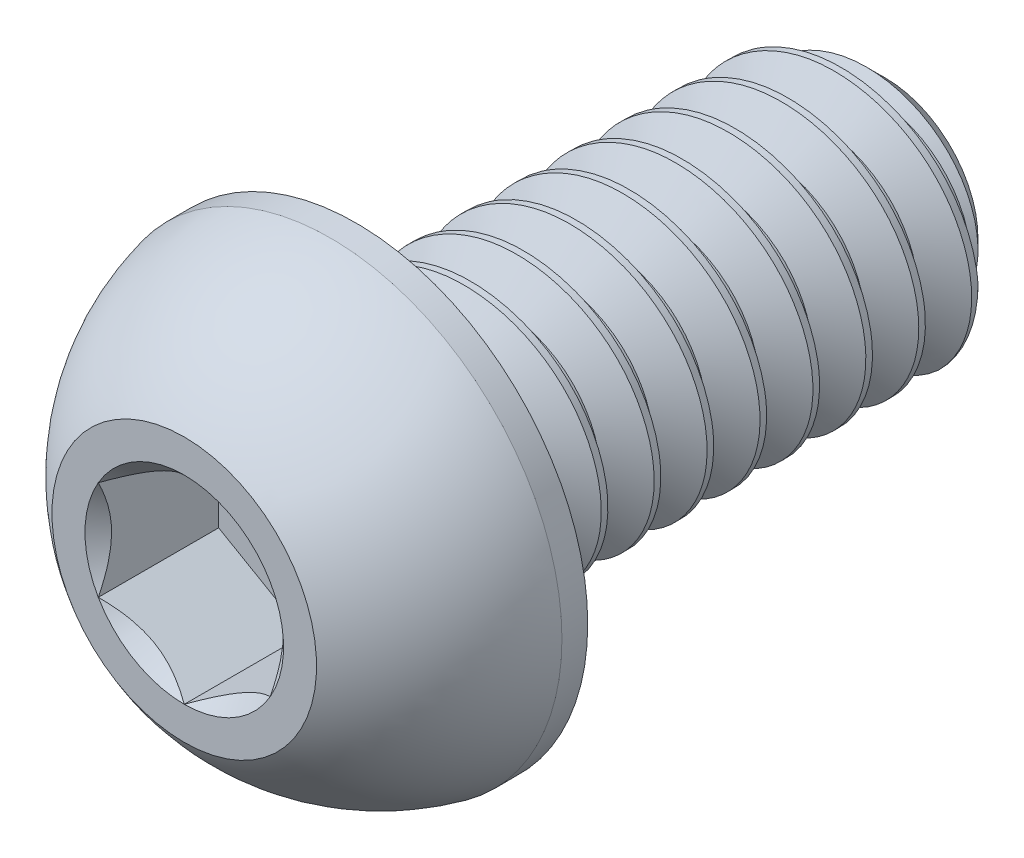
SolidWorks part; units mm, degrees
ref_plane "Front" through (0, 0, 0) normal (0, 0, 1) x (1, 0, 0)
ref_plane "Top" through (0, 0, 0) normal (0, 1, 0) x (1, 0, 0)
ref_plane "Right" through (0, 0, 0) normal (1, 0, 0) x (0, 0, -1)
sketch "Sketch1" plane through (0, 0, 0) normal (1, 0, 0) x (0, 0, -1)
  line L2 (1.3, 1) -> (5.3, 1)
  line L3 (5.3, 1) -> (5.3, 0)
  line L4 (5.3, 0) -> (1.3, 0)
  line L6 (1.105, 1.75) -> (1.3, 1.75) construction
  line L7 (5.3, 1) -> (5.3, -1) construction
  line L8 (0, 0) -> (1.3, 0) construction
  line L9 (1.3, 1.75) -> (1.3, -1.75) construction
  line L11 (1.3, 1) -> (1.3, 0)
  line L13 (0, 0.65) -> (0, -0.65) construction
  line L14 (0, 0.65) -> (0, 1) construction
  arc A3 (0, 1) -> (1.105, 1.75) centre (1.4858, 0) cw construction
  dimension "D1" = 0.195
  dimension "Head Ht" = 1.3
  dimension "Head Dia" = 3.5
  dimension "Dia" = 2
  dimension "Lg" = 4
  dimension "Hex" = 1.3
revolve "Revolve1" add sketch "Sketch1" angle 360 mid plane about L4
sketch "Sketch3" plane through (0, 0, -5.3) normal (0, 0, -1) x (-1, 0, 0)
  circle A0 centre (0, 0) radius 1
curve "Helix/Spiral1" pitch 0.4 height 4.4 radius 1 centre (0, 0, -5.3) axis (0, 0, 1) start towards (0, 1, 0)
sketch "Sketch2" plane through (0, 0, 0) normal (1, 0, 0) x (0, 0, -1)
  line L0 (5.3, 1) -> (5.65, 1)
  line L1 (5.65, 1) -> (5.5, 0.7402)
  line L2 (5.5, 0.7402) -> (5.45, 0.7402)
  line L3 (5.45, 0.7402) -> (5.3, 1)
  line L4 (5.375, 0.8701) -> (5.575, 0.8701) construction
  dimension "D1" = 60
  dimension "D2" = 0.05
  dimension "D3" = 0.2
chamfer "Chamfer1" distance 0.3 angle 45 1 edges at (0, 1, -5.3)
sweep "Cut-Sweep1" cut profiles "Sketch2" path "Helix/Spiral1" align with end faces yes
sketch "Sketch7" plane through (0, 0, 0) normal (1, 0, 0) x (0, 0, -1)
  line L6 (1.105, 1.75) -> (1.3, 1.75) construction
  line L8 (0, 0) -> (1.3, 0) construction
  line L11 (1.3, 1.75) -> (1.3, -1.75) construction
  line L12 (1.105, 1.75) -> (1.3, 1.75)
  line L13 (0, 0) -> (1.3, 0)
  line L14 (0, 0.65) -> (0, -0.65) construction
  line L15 (1.3, 1.75) -> (1.3, 0)
  line L16 (0, 1) -> (0, 0)
  arc A2 (1.105, 1.75) -> (0, 1) centre (1.4858, 0) ccw construction
  arc A3 (1.105, 1.75) -> (0, 1) centre (1.4858, 0) ccw
revolve "Revolve2" add sketch "Sketch7" angle 360 mid plane about L13
sketch "Sketch5" plane through (0, 0, 0) normal (0, 0, 1) x (1, 0, 0)
  line L1 (0.65, -0.3753) -> (0.65, 0.3753)
  line L2 (0.65, 0.3753) -> (0, 0.7506)
  line L3 (0, 0.7506) -> (-0.65, 0.3753)
  line L4 (-0.65, 0.3753) -> (-0.65, -0.3753)
  line L5 (-0.65, -0.3753) -> (0, -0.7506)
  line L6 (0, -0.7506) -> (0.65, -0.3753)
  circle A0 centre (0, 0) radius 0.65 construction
extrude "Cut-Extrude2" cut sketch "Sketch5" against normal blind 0.91
sketch "Sketch6" plane through (0, 0, 0) normal (0, 0, 1) x (1, 0, 0)
  circle A0 centre (0, 0) radius 0.7506
extrude "Cut-Extrude3" cut sketch "Sketch6" against normal blind 0.91 draft 45
sketch "Sketch9" [suppressed] plane through (0, 0, -4.2164) normal (0, 0, 1) x (1, 0, 0)
  circle A2 centre (0, 0) radius 3.9687
extrude "Boss-Extrude2" [suppressed] add sketch "Sketch9" against normal offset from surface (9.525 mm away) 28.575 up to face at (0, 0.7, -5.3)
sketch "Sketch10" plane through (0, 0, 0) normal (1, 0, 0) x (0, 0, -1)
  line L0 (5.3, 1) -> (5.3, -1) construction
  point P0 (4.7, -1)
  dimension "D1" = 0.6
equation "\"D3@Helix/Spiral1\" = \"Lg@Sketch1\" + \"D4@Helix/Spiral1\""
equation "\"D2@Sketch2\" = \"D4@Helix/Spiral1\" * .125"
equation "\"D3@Sketch2\" = \"D4@Helix/Spiral1\" * .5"
equation "\"D1@Chamfer1\" = \"D4@Helix/Spiral1\" * .75"
equation "\"D1@Cut-Extrude2\" = \"Head Ht@Sketch1\" * .7"
equation "\"D1@Sketch1\" = \"Head Ht@Sketch1\" * .15"
equation "\"D1@Sketch10\" = \"D4@Helix/Spiral1\" * 1.5"
equation "\"D1@Cut-Extrude3\" = \"D1@Cut-Extrude2\""
